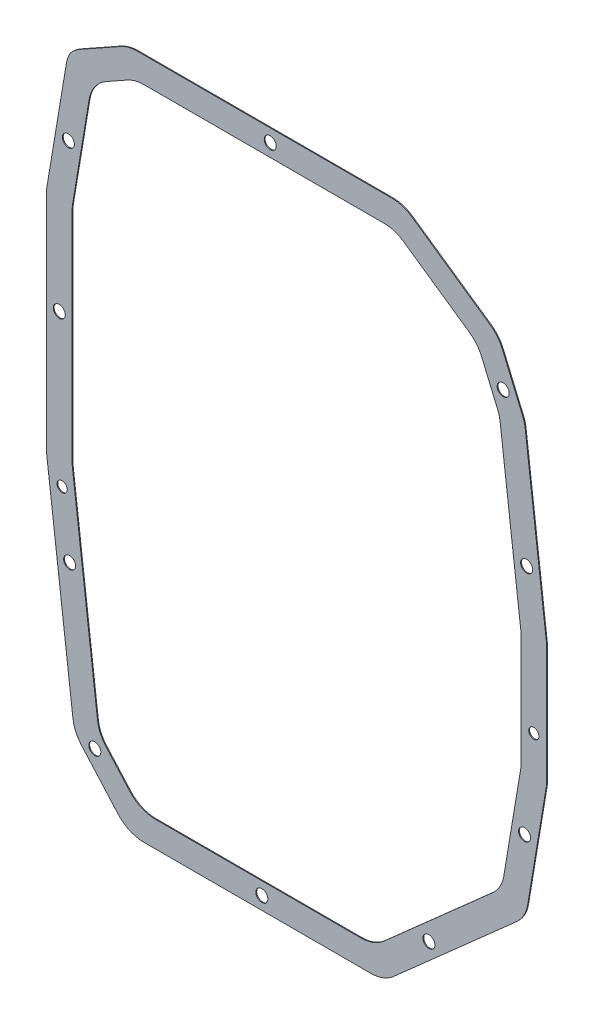
SolidWorks part; units mm, degrees
other "Annotazione1"
sketch "Schizzo14" plane through (279.1827, 388.4513, 77.1126) normal (0.6451, 0.2249, 0.7302) x (0.7332, 0.0867, -0.6745)
ref_plane "Piano frontale" through (0, 0, 0) normal (0, 0, 1) x (1, 0, 0)
ref_plane "Piano superiore" through (0, 0, 0) normal (0, 1, 0) x (1, 0, 0)
ref_plane "Piano destro" through (0, 0, 0) normal (1, 0, 0) x (0, 0, -1)
sketch "Schizzo1" plane through (0, 0, 0) normal (0, 0, 1) x (1, 0, 0)
  line L0 (59.972, -9.5487) -> (184.1074, -9.5487)
  line L4 (195.1963, 388.4513) -> (251.0014, 349.7307)
  line L5 (251.0014, 349.7307) -> (266.2641, 313.838)
  line L6 (266.9069, 63.8243) -> (184.1074, -9.5487)
  line L12 (266.2641, 313.838) -> (279.1827, 207.629)
  line L13 (279.1827, 207.629) -> (279.1827, 137.3778)
  line L14 (279.1827, 137.3778) -> (266.9069, 63.8243)
  line L15 (195.1963, 388.4513) -> (34.9751, 388.4513)
  line L18 (-12.8173, 291.7963) -> (-12.8173, 270.1406)
  line L19 (-12.8173, 270.1406) -> (-12.8173, 159.5427)
  line L22 (-12.8173, 159.5427) -> (-8.0968, 120.7332)
  line L23 (-8.0968, 120.7332) -> (-1.2777, 64.671)
  line L24 (-1.2777, 64.671) -> (3.4183, 26.0624)
  line L25 (3.4183, 26.0624) -> (34.9751, -9.5487)
  line L26 (34.9751, -9.5487) -> (59.972, -9.5487)
  line L27 (-12.8173, 291.7963) -> (-0.4488, 365.9057)
  line L28 (-0.4488, 365.9057) -> (2.5692, 370.2553)
  line L29 (2.5692, 370.2553) -> (34.9751, 388.4513)
  dimension "D1" = 398
  dimension "D2" = 292
extrude "Estrusione-Estrusione1" add sketch "Schizzo1" along normal blind 77
sketch "Schizzo2" plane through (0, 0, 77) normal (0, 0, 1) x (1, 0, 0)
  line L0 (119.1827, 251.9513) -> (119.1827, 109.4513) construction
  line L1 (227.1858, 174.3461) -> (119.1827, 109.4513) construction
  line L2 (119.1827, 109.4513) -> (200.5095, 109.4513) construction
  line L3 (34.9751, -9.5487) -> (184.1074, -9.5487) construction
  line L6 (-12.8173, 291.7963) -> (-12.8173, 159.5427) construction
  circle A0 centre (119.1827, 251.9513) radius 50
  circle A1 centre (227.1858, 174.3461) radius 36
  circle A2 centre (119.1827, 109.4513) radius 26
  dimension "D1" = 72
  dimension "D2" = 52
  dimension "D3" = 100
  dimension "D7" = 119
  dimension "D8" = 132
  dimension "D4" = 142.5
  dimension "D5" = 126
  dimension "D6" = 31
extrude "Taglio-Estrusione1" cut sketch "Schizzo2" against normal through all
sketch "Schizzo4" plane through (0, 0, 0) normal (0, 0, -1) x (-1, 0, 0)
  line L482 (-190.5021, 373.4513) -> (-238.8923, 339.8755)
  line L483 (-238.8923, 339.8755) -> (-251.63, 309.9207)
  line L484 (-251.63, 309.9207) -> (-264.1827, 206.7201)
  line L485 (-264.1827, 206.7201) -> (-264.1827, 138.6209)
  line L486 (-264.1827, 138.6209) -> (-252.9855, 71.5298)
  line L487 (-252.9855, 71.5298) -> (-178.4176, 5.4513)
  line L488 (-178.4176, 5.4513) -> (-41.7249, 5.4513)
  line L489 (-41.7249, 5.4513) -> (-17.7443, 32.5128)
  line L490 (-17.7443, 32.5128) -> (-2.1827, 160.4516)
  line L491 (-2.1827, 160.4516) -> (-2.1827, 290.5532)
  line L492 (-2.1827, 290.5532) -> (-13.6521, 359.2755)
  line L494 (-13.6521, 359.2755) -> (-38.8983, 373.4513)
  line L495 (-38.8983, 373.4513) -> (-190.5021, 373.4513)
  line L496 (-190.5021, 373.4513) -> (-238.8923, 339.8755)
  line L497 (-238.8923, 339.8755) -> (-251.63, 309.9207)
  line L498 (-251.63, 309.9207) -> (-264.1827, 206.7201)
  line L499 (-264.1827, 206.7201) -> (-264.1827, 138.6209)
  line L500 (-264.1827, 138.6209) -> (-252.9855, 71.5298)
  line L501 (-252.9855, 71.5298) -> (-178.4176, 5.4513)
  line L502 (-178.4176, 5.4513) -> (-41.7249, 5.4513)
  line L503 (-41.7249, 5.4513) -> (-17.7443, 32.5128)
  line L504 (-17.7443, 32.5128) -> (-2.1827, 160.4516)
  line L505 (-2.1827, 160.4516) -> (-2.1827, 290.5532)
  line L506 (-2.1827, 290.5532) -> (-13.6521, 359.2755)
  line L508 (-13.6521, 359.2755) -> (-38.8983, 373.4513)
  line L509 (-38.8983, 373.4513) -> (-190.5021, 373.4513)
  dimension "D1" = 15
extrude "Taglio-Estrusione2" cut sketch "Schizzo4" against normal blind 48
sketch "Schizzo8" plane through (0, 0, 77) normal (0, 0, 1) x (1, 0, 0)
  line L0 (227.1858, 174.3461) -> (182.1858, 174.3461) construction
  line L1 (227.1858, 174.3461) -> (249.6858, 135.375) construction
  circle A3 centre (227.1858, 174.3461) radius 45
  circle A4 centre (119.1827, 251.9513) radius 58
  circle A5 centre (119.1827, 109.4513) radius 35
  point P2 (182.1858, 174.3461)
  point P5 (119.1827, 309.9513)
  point P6 (249.6858, 135.375)
  point P7 (249.6858, 213.3173)
  point P8 (227.1858, 174.3461)
  point P13 (119.1827, 144.4513)
  point P14 (169.4121, 222.9513)
  point P15 (68.9532, 222.9513)
  point P16 (119.1827, 251.9513)
  point P21 (149.4936, 91.9513)
  point P22 (88.8718, 91.9513)
  point P23 (119.1827, 109.4513)
  point P25 (227.1858, 174.3461)
  point P26 (227.1858, 174.3461)
  dimension "D1" = 90
  dimension "D2" = 3
  dimension "D3" = 120
  dimension "100" = 116
  dimension "D5" = 0
  dimension "82" = 70
  dimension "D7" = 0
  dimension "D8" = 0
  dimension "D9" = 0
  dimension "D4" = 3
  dimension "D6" = 3
hole_wizard "Foro filettato M8-1" positions "Schizzo3D2" profile "Schizzo9" tap size "M8" standard "ISO"
sketch3d "Schizzo3D2"
  point P0 (119.1827, 309.9513, 77)
  point P3 (68.9532, 222.9513, 77)
  point P6 (169.4121, 222.9513, 77)
  point P9 (182.1858, 174.3461, 77)
  point P12 (249.6858, 213.3173, 77)
  point P15 (249.6858, 135.375, 77)
  point P18 (119.1827, 144.4513, 77)
  point P21 (88.8718, 91.9513, 77)
  point P24 (149.4936, 91.9513, 77)
cosmetic thread "Filettatura del foro1" parameters "D1"=20, "D2"=8
cosmetic thread "Filettatura del foro2" parameters "D1"=20, "D2"=8
cosmetic thread "Filettatura del foro3" parameters "D1"=20, "D2"=8
cosmetic thread "Filettatura del foro4" parameters "D1"=20, "D2"=8
cosmetic thread "Filettatura del foro5" parameters "D1"=20, "D2"=8
cosmetic thread "Filettatura del foro6" parameters "D1"=20, "D2"=8
cosmetic thread "Filettatura del foro7" parameters "D1"=20, "D2"=8
cosmetic thread "Filettatura del foro8" parameters "D1"=20, "D2"=8
cosmetic thread "Filettatura del foro9" parameters "D1"=20, "D2"=8
sketch "Schizzo9" plane through (119.1827, 309.9513, 77) normal (1, 0, 0) x (0, -1, 0)
  line L0 (0, 0) -> (0, 25.0429)
  line L1 (0, 25.0429) -> (3.4, 23)
  line L2 (3.4, 23) -> (3.4, 0.625)
  line L3 (3.4, 0.625) -> (4.025, 0)
  line L5 (4.025, 0) -> (0, 0)
  line L6 (-3.4, 0.625) -> (-4.025, 0) construction
  line L10 (0, 25.0429) -> (-3.4, 23) construction
  line L11 (0, -6.35) -> (0, 107.95) construction
  dimension "Tap Drill Dia." = 6.8
  dimension "Tap Drill Depth" = 23
  dimension "Near C'Sink Dia." = 8.05
  dimension "Near C'Sink Angle" = 90
  dimension "Drill Angle" = 118
sketch "Schizzo10" plane through (0, 0, 0) normal (0, 0, -1) x (-1, 0, 0)
  line L0 (-279.1827, 207.629) -> (-266.2641, 313.838) construction
  line L1 (-238.8923, 339.8755) -> (-251.63, 309.9207) construction
  line L2 (-41.7249, 5.4513) -> (-17.7443, 32.5128) construction
  line L3 (-117.8071, 388.4513) -> (-117.8071, 377.4513) construction
  line L4 (-195.1963, 388.4513) -> (-34.9751, 388.4513) construction
  line L5 (-7.3292, 321.3901) -> (7.3349, 324.6457) construction
  line L6 (0.4488, 365.9057) -> (12.8173, 291.7963) construction
  line L7 (-246.6828, 321.5548) -> (-260.949, 326.3373) construction
  line L8 (-238.8923, 339.8755) -> (-251.63, 309.9207) construction
  line L9 (-266.2641, 313.838) -> (-251.0014, 349.7307) construction
  line L10 (-260.0187, 240.9543) -> (-274.9437, 242.4794) construction
  line L11 (-251.63, 309.9207) -> (-264.1827, 206.7201) construction
  line L12 (-2.1827, 234.1317) -> (12.8173, 234.1317) construction
  line L13 (-2.1827, 160.4516) -> (-2.1827, 290.5532) construction
  line L14 (12.8173, 291.7963) -> (12.8173, 159.5427) construction
  line L15 (-8.2207, 110.8103) -> (6.6695, 108.9992) construction
  line L16 (-17.7443, 32.5128) -> (-2.1827, 160.4516) construction
  line L17 (12.8173, 159.5427) -> (-3.4183, 26.0624) construction
  line L18 (-112.9191, 5.4513) -> (-112.9191, -9.5487) construction
  line L19 (-34.9751, -9.5487) -> (-184.1074, -9.5487) construction
  line L20 (-203.9893, 28.1118) -> (-216.4303, 19.0943) construction
  line L21 (-252.9855, 71.5298) -> (-178.4176, 5.4513) construction
  line L22 (-258.8828, 106.865) -> (-273.6267, 104.0879) construction
  line L23 (-210.4191, 23.4513) -> (-15.4191, 23.4513) construction
  line L24 (-264.1827, 138.6209) -> (-252.9855, 71.5298) construction
  line L25 (-184.1074, -9.5487) -> (-266.9069, 63.8243) construction
  line L26 (-2.1827, 290.5532) -> (-13.6521, 359.2755) construction
  line L27 (-38.8983, 373.4513) -> (-190.5021, 373.4513) construction
  line L30 (-178.4176, 5.4513) -> (-41.7249, 5.4513) construction
  line L31 (-251.63, 309.9207) -> (-264.1827, 206.7201) construction
  circle A0 centre (-117.8071, 380.9513) radius 3.5
  circle A1 centre (-253.772, 324.0494) radius 3.5
  circle A4 centre (5.3173, 234.1317) radius 3.5
  circle A5 centre (-266.2547, 105.4764) radius 3.5
  circle A6 centre (-0.7392, 110.2036) radius 3.5
  circle A10 centre (-112.9191, -2.0487) radius 3.5
  circle A11 centre (0.0028, 323.0179) radius 3.5
  circle A12 centre (-267.4812, 241.7168) radius 3.5
  circle A13 centre (-210.4191, 23.4513) radius 3.5
  circle A16 centre (-15.4191, 23.4513) radius 3.5
  point P15 (-266.2547, 105.4764)
  dimension "D1" = 7
  dimension "10" = 7
  dimension "D2" = 7
  dimension "D3" = 7
  dimension "D4" = 7
  dimension "6" = 7
  dimension "D5" = 7
  dimension "D6" = 7
  dimension "D7" = 25.5
  dimension "D8" = 7
  dimension "D9" = 7.5
  dimension "D16" = 7.5
  dimension "D17" = 7
  dimension "D18" = 7.75
  dimension "D10" = 7.5
  dimension "D11" = 7.5
  dimension "D12" = 7.5
  dimension "D13" = 7.5
  dimension "D14" = 7.5
  dimension "D15" = 7.5
  dimension "D19" = 97.5
  dimension "D20" = 25.5
  dimension "D21" = 97.5
extrude "Taglio-Estrusione3" cut sketch "Schizzo10" against normal through all
fillet "Raccordo1" radius 20 14 edges at (34.9751, 388.4513, 38.5) (2.5692, 370.2553, 38.5) (-0.4488, 365.9057, 38.5) (-12.8173, 291.7963, 38.5) (-12.8173, 159.5427, 38.5) (3.4183, 26.0624, 38.5) (34.9751, -9.5487, 38.5) (184.1074, -9.5487, 38.5) (266.9069, 63.8243, 38.5) (279.1827, 137.3778, 38.5) (279.1827, 207.629, 38.5) (266.2641, 313.838, 38.5) (251.0014, 349.7307, 38.5) (195.1963, 388.4513, 38.5)
fillet "Raccordo2" radius 2 27 edges at (-0.3253, 364.8301, 77) (-6.8658, 327.4564, 77) (-12.749, 291.7906, 77) (-12.8173, 225.4467, 77) (-12.7807, 159.5449, 77) (-5.0025, 95.2939, 77) (4.283, 26.4517, 77) (18.2787, 9.2928, 77) (35.7677, -7.7872, 77) (110.2479, -9.5487, 77) (183.6142, -8.2485, 77) (225.6973, 27.3063, 77) (265.8434, 64.4129, 77) (273.491, 103.2744, 77) (279.1143, 137.3834, 77) (279.1827, 172.7262, 77) (279.1461, 207.6268, 77) (272.821, 259.9309, 77) (266.0718, 313.7865, 77) (259.209, 330.4291, 77) (250.3678, 349.215, 77) (3.6392, 370.4906, 77) (18.4991, 379.2, 77) (35.1453, 387.8005, 77) (114.5717, 388.4513, 77) (194.9106, 387.5385, 77) (223.298, 368.9528, 77)
sketch "Schizzo11" plane through (0, 0, 48) normal (0, 0, -1) x (-1, 0, 0)
  circle A0 centre (-119.1827, 251.9513) radius 43
  circle A1 centre (-119.1827, 251.9513) radius 50
  dimension "D1" = 86
  dimension "D2" = 100
extrude "Estrusione-Estrusione2" add sketch "Schizzo11" against normal blind 4.5
sketch "Schizzo12" plane through (0, 0, 48) normal (0, 0, -1) x (-1, 0, 0)
  line L0 (-267.1858, 219.3461) -> (-227.1858, 219.3461)
  line L1 (-227.1858, 129.3461) -> (-267.1858, 129.3461)
  line L3 (-267.1858, 219.3461) -> (-265.4743, 179.3461)
  line L4 (-265.4743, 179.3461) -> (-267.1858, 129.3461)
  arc A0 (-227.1858, 129.3461) -> (-227.1858, 219.3461) centre (-227.1858, 174.3461) ccw
  circle A1 centre (-227.1858, 174.3461) radius 33.5
  dimension "D1" = 67
  dimension "D2" = 90
extrude "Estrusione-Estrusione4" add sketch "Schizzo12" against normal blind 6 from offset 5
sketch "Schizzo13" plane through (0, 0, 48) normal (0, 0, -1) x (-1, 0, 0)
  circle A0 centre (-119.1827, 109.4513) radius 26
  circle A1 centre (-119.1827, 109.4513) radius 23
  dimension "D1" = 46
  dimension "D2" = 52
extrude "Estrusione-Estrusione5" add sketch "Schizzo13" against normal blind 4
sketch "Schizzo15" plane through (0, 0, 0) normal (0, 0, -1) x (-1, 0, 0)
  line L0 (-264.1827, 206.7201) -> (-264.1827, 138.6209) construction
  line L1 (-271.6827, 159.3461) -> (31.6889, 159.3461) construction
  line L3 (12.671, 158.3397) -> (-2.6659, 32.2481) construction
  circle A0 centre (-271.6827, 159.3461) radius 3
  circle A1 centre (-227.1858, 174.3461) radius 33.5 construction
  circle A2 centre (3.6569, 146.3461) radius 3
  dimension "D1" = 15
  dimension "D2" = 7.5
  dimension "D3" = 6
  dimension "D4" = 6
  dimension "D5" = 7.5
  dimension "D6" = 13
extrude "Taglio-Estrusione4" cut sketch "Schizzo15" against normal blind 11
fillet "Raccordo4" radius 20 13 edges at (252.9855, 71.5298, 24) (264.1827, 206.7201, 21.5) (264.1827, 138.6209, 21.5) (178.4176, 5.4513, 24) (41.7249, 5.4513, 24) (17.7443, 32.5128, 24) (2.1827, 160.4516, 24) (2.1827, 290.5532, 24) (13.6521, 359.2755, 24) (38.8983, 373.4513, 24) (190.5021, 373.4513, 24) (251.63, 309.9207, 24) (238.8923, 339.8755, 24)
sketch "Schizzo16" plane through (0, 388.4513, 0) normal (0, 1, 0) x (1, 0, 0)
  circle A0 centre (60, -30) radius 12.3293
  dimension "D1" = 30
  dimension "D2" = 60
hole_wizard "Foro filettato M20x1.5-1" positions "Schizzo3D3" profile "Schizzo17" tap size "M20x1.5" standard "ISO"
sketch3d "Schizzo3D3"
  point P0 (60, 388.4513, 30)
sketch "Schizzo17" plane through (60, 388.4513, 30) normal (1, 0, 0) x (0, 0, 1)
  line L0 (0, 0) -> (0, 50.058)
  line L1 (0, 50.058) -> (9.25, 44.5)
  line L2 (9.25, 44.5) -> (9.25, 0.775)
  line L3 (9.25, 0.775) -> (10.025, 0)
  line L5 (10.025, 0) -> (0, 0)
  line L6 (-9.25, 0.775) -> (-10.025, 0) construction
  line L10 (0, 50.058) -> (-9.25, 44.5) construction
  line L11 (0, -6.35) -> (0, 107.95) construction
  dimension "Tap Drill Dia." = 18.5
  dimension "Tap Drill Depth" = 44.5
  dimension "Near C'Sink Dia." = 20.05
  dimension "Near C'Sink Angle" = 90
  dimension "Drill Angle" = 118
cosmetic thread "Filettatura del foro10" parameters "D1"=15, "D2"=20
sketch "Schizzo18" plane through (6.4923, 0.7897, 0) normal (-0.9927, -0.1207, 0) x (0, 0, 1)
  line L0 (0, 158.7112) -> (0, 31.6903) construction
  line L1 (0, 31.6903) -> (75, 31.6903) construction
  circle A0 centre (30, 61.6903) radius 12.2065
  dimension "D1" = 30
  dimension "D2" = 30
hole_wizard "Foro filettato G1/2-1" positions "Schizzo3D4" profile "Schizzo19" tap size "G1/2" standard "ISO" end condition up to next
sketch3d "Schizzo3D4"
  point P0 (-0.9564, 62.0287, 30)
sketch "Schizzo19" plane through (-0.9564, 62.0287, 30) normal (0, 0, 1) x (0.1207, -0.9927, 0)
  line L0 (0, 0) -> (0, 15)
  line L1 (0, 15) -> (9.5, 15)
  line L2 (9.5, 15) -> (9.5, 1.0025)
  line L3 (9.5, 1.0025) -> (10.5025, 0)
  line L5 (10.5025, 0) -> (0, 0)
  line L6 (-9.5, 1.0025) -> (-10.5025, 0) construction
  line L11 (0, -6.35) -> (0, 107.95) construction
  dimension "Thru Tap Drill Dia." = 19
  dimension "Thru Tap Drill Depth" = 15
  dimension "Near C'Sink Dia." = 21.005
  dimension "Near C'Sink Angle" = 90
cosmetic thread "Filettatura del foro11" parameters "D2"=20.955
sketch "Schizzo20" plane through (0, -9.5487, 0) normal (0, -1, 0) x (1, 0, 0)
  circle A0 centre (60, 30) radius 12.3293
hole_wizard "Foro filettato M20x1.5-3" positions "Schizzo3D6" profile "Schizzo23" tap size "M20x1.5" standard "ISO" end condition up to next
sketch3d "Schizzo3D6"
  point P0 (60, -9.5487, 30)
sketch "Schizzo23" plane through (60, -9.5487, 30) normal (1, 0, 0) x (0, 0, -1)
  line L0 (0, 0) -> (0, 15)
  line L1 (0, 15) -> (9.25, 15)
  line L2 (9.25, 15) -> (9.25, 0.775)
  line L3 (9.25, 0.775) -> (10.025, 0)
  line L5 (10.025, 0) -> (0, 0)
  line L6 (-9.25, 0.775) -> (-10.025, 0) construction
  line L11 (0, -6.35) -> (0, 107.95) construction
  dimension "Thru Tap Drill Dia." = 18.5
  dimension "Thru Tap Drill Depth" = 15
  dimension "Near C'Sink Dia." = 20.05
  dimension "Near C'Sink Angle" = 90
cosmetic thread "Filettatura del foro13" parameters "D2"=20
fillet "Raccordo6" radius 4 23 edges at (177.9244, 6.7515, 48) (215.8917, 38.6591, 48) (251.9219, 72.1185, 48) (258.3927, 103.9288, 48) (257.3093, 263.2293, 48) (251.4377, 309.8692, 48) (245.8374, 323.5429, 48) (238.2587, 339.3599, 48) (214.8963, 356.5252, 48) (190.2164, 372.5385, 48) (114.1862, 373.4513, 48) (39.0685, 372.8005, 48) (28.1733, 367.4292, 48) (15.4345, 358.0237, 48) (7.2649, 321.0048, 48) (2.251, 290.5475, 48) (2.1827, 225.2796, 48) (2.2193, 160.4539, 48) (9.6605, 98.9736, 48) (18.609, 32.9022, 48) (28.8166, 20.018, 48) (42.5175, 7.2128, 48) (110.7779, 5.4513, 48)
sketch "Schizzo24" plane through (0, 0, 77) normal (0, 0, 1) x (1, 0, 0)
  line L0 (-76.0983, 422.3549) -> (-76.0983, -50.5088)
  line L1 (-76.0983, -50.5088) -> (348.6015, -50.5088)
  line L2 (348.6015, -50.5088) -> (348.6015, 422.3549)
  line L3 (348.6015, 422.3549) -> (-76.0983, 422.3549)
extrude "Taglio-Estrusione8" cut sketch "Schizzo24" against normal blind 76.5
